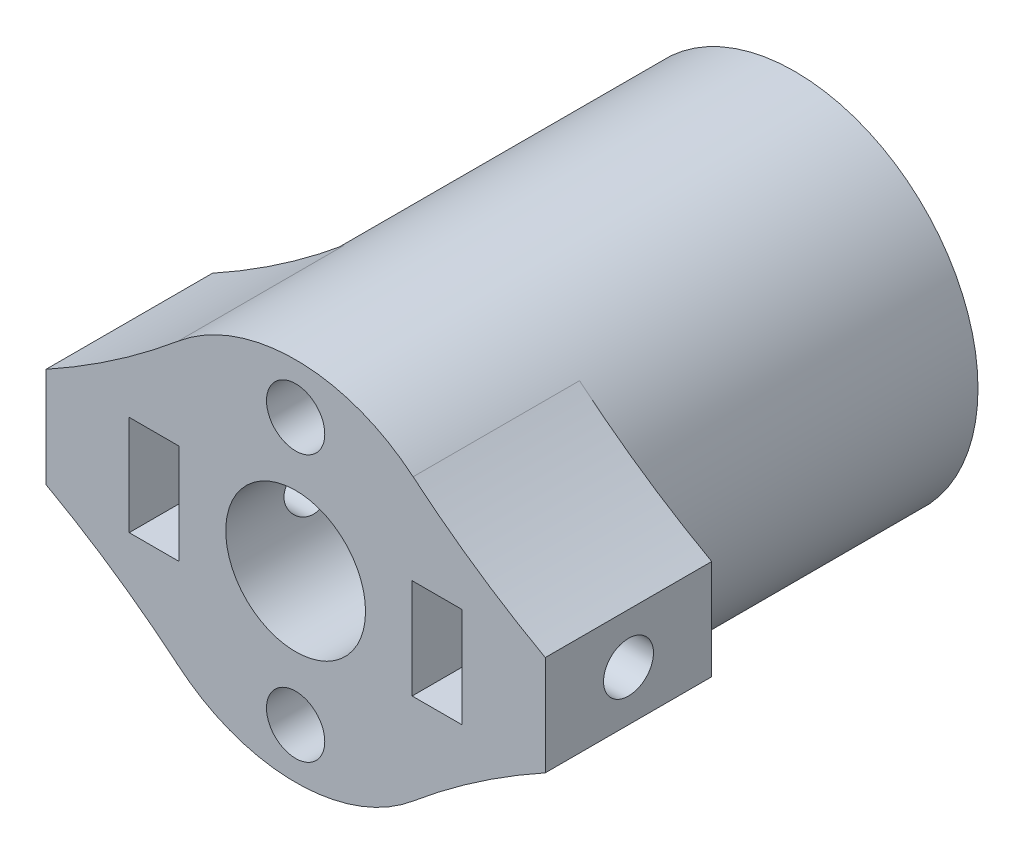
SolidWorks part; units mm, degrees
ref_plane "Front Plane" through (0, 0, 0) normal (0, 0, 1) x (1, 0, 0)
ref_plane "Top Plane" through (0, 0, 0) normal (0, 1, 0) x (1, 0, 0)
ref_plane "Right Plane" through (0, 0, 0) normal (1, 0, 0) x (0, 0, -1)
sketch "Sketch1" plane through (0, 0, 0) normal (0, 0, 1) x (1, 0, 0)
  line L0 (0, 0) -> (0, 8) construction
  line L1 (0, 0) -> (0, -8) construction
  circle A0 centre (0, 0) radius 11
  circle A1 centre (0, 8) radius 1.75
  circle A2 centre (0, -8) radius 1.75
  dimension "D1" = 22
  dimension "D2" = 8
  dimension "D3" = 8
  dimension "D4" = 3.5
  dimension "D5" = 3.5
extrude "Boss-Extrude1" add sketch "Sketch1" along normal blind 19
sketch "Sketch2" plane through (0, 0, 0) normal (0, 0, -1) x (-1, 0, 0)
  circle A0 centre (0, 8) radius 1.75 construction
  circle A1 centre (0, 0) radius 11
  circle A2 centre (0, 0) radius 11
  circle A3 centre (0, 8) radius 1.75
  circle A4 centre (0, -8) radius 1.75 construction
  circle A5 centre (0, -8) radius 1.75
  dimension "D1" = 0
extrude "Boss-Extrude2" add sketch "Sketch2" along normal blind 11
sketch "Sketch6" plane through (0, 0, 19) normal (0, 0, 1) x (1, 0, 0)
  line L0 (-4.0792, 1) -> (-5, 1)
  line L1 (-5, 1) -> (-5, -1)
  line L2 (-5, -1) -> (-4.0792, -1)
  arc A0 (-4.0792, -1) -> (-4.0792, 1) centre (0, 0) ccw
  dimension "D1" = 8.4
  dimension "D2" = 5
  dimension "D3" = 1
  dimension "D4" = 2
extrude "Cut-Extrude3" cut sketch "Sketch6" against normal blind 20
sketch "Sketch7" plane through (0, 0, -11) normal (0, 0, -1) x (-1, 0, 0)
  circle A0 centre (0, 0) radius 5
  dimension "D1" = 10
extrude "Cut-Extrude4" cut sketch "Sketch7" against normal blind 5
sketch "Sketch8" plane through (0, 0, -6) normal (0, 0, -1) x (-1, 0, 0)
  circle A0 centre (0, 0) radius 2.2
  dimension "D1" = 4.4
extrude "Cut-Extrude5" cut sketch "Sketch8" against normal blind 5
sketch "Sketch9" plane through (0, 0, 19) normal (0, 0, 1) x (1, 0, 0)
  line L0 (-4.0792, 1) -> (-5, 1) construction
  line L1 (-5, -1) -> (-4.0792, -1) construction
  line L2 (-5, 1) -> (-5, -1) construction
  line L3 (-5, -1) -> (-4.0792, -1)
  line L4 (-5, 1) -> (-5, -1)
  line L5 (-4.0792, 1) -> (-5, 1)
  arc A1 (-4.0792, 1) -> (-4.0792, -1) centre (0, 0) ccw
extrude "Boss-Extrude3" add sketch "Sketch9" against normal up to surface (20 mm away) up to face at (-2.2, 0, -1)
sketch "Sketch11" plane through (0, 0, 19) normal (0, 0, 1) x (1, 0, 0)
  line L0 (0, 0) -> (0, -8) construction
  line L1 (-10, 3) -> (-7, 3)
  line L2 (-10, 3) -> (-10, -3)
  line L3 (-10, -3) -> (-7, -3)
  line L4 (-7, 3) -> (-7, -3)
  line L5 (10, -3) -> (7, -3)
  line L6 (7, 3) -> (7, -3)
  line L7 (10, 3) -> (7, 3)
  line L8 (10, 3) -> (10, -3)
  dimension "D1" = 3
  dimension "D2" = 6
  dimension "D3" = 3
  dimension "D4" = 7
extrude "Cut-Extrude6" cut sketch "Sketch11" against normal blind 10
sketch "Sketch12" plane through (0, 0, 0) normal (1, 0, 0) x (0, 0, -1)
  line L0 (-19, 11) -> (-19, -11) construction
  line L1 (-19, -11) -> (11, -11) construction
  circle A0 centre (-14, 0) radius 1.5
  dimension "D1" = 5
  dimension "D2" = 3
  dimension "D3" = 11
extrude "Cut-Extrude7" cut sketch "Sketch12" against normal through all both and the other way through all
sketch "Sketch13" plane through (10, 0, 0) normal (-1, 0, 0) x (0, 0, 1)
  line L4 (19, -3) -> (19, 3)
  line L5 (19, 3) -> (9, 3)
  line L6 (9, 3) -> (9, -3)
  line L7 (9, -3) -> (19, -3)
  line L8 (19, -3) -> (19, 3)
  line L9 (19, 3) -> (9, 3)
  line L10 (9, 3) -> (9, -3)
  line L11 (9, -3) -> (19, -3)
  circle A0 centre (14, 0) radius 1.5 construction
  circle A1 centre (14, 0) radius 1.5
  dimension "D1" = 0
extrude "Boss-Extrude4" add sketch "Sketch13" against normal blind 5
mirror "Mirror1" about plane through (0, 0, 0) normal (1, 0, 0) of "Boss-Extrude4"
fillet "Fillet1" radius 50 4 edges at (-10.583, -3, 14) (-10.583, 3, 14) (10.583, 3, 14) (10.583, -3, 14)
